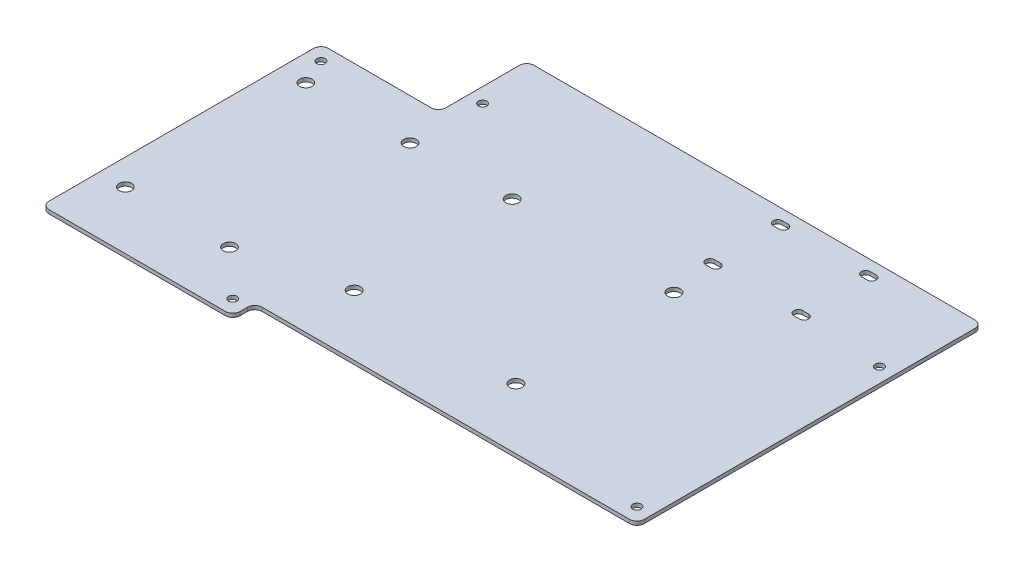
SolidWorks part; units mm, degrees
ref_plane "Front Plane" through (0, 0, 0) normal (0, 0, 1) x (1, 0, 0)
ref_plane "Top Plane" through (0, 0, 0) normal (0, 1, 0) x (1, 0, 0)
ref_plane "Right Plane" through (0, 0, 0) normal (1, 0, 0) x (0, 0, -1)
sketch "Sketch1" plane through (0, 0, 0) normal (0, 1, 0) x (1, 0, 0)
  line L1 (0, 0) -> (247.65, 0)
  line L2 (0, 0) -> (0, 120.65)
  line L3 (50.8, 158.75) -> (247.65, 158.75)
  line L4 (247.65, 0) -> (247.65, 158.75)
  line L15 (0, 120.65) -> (50.8, 120.65)
  line L16 (50.8, 158.75) -> (50.8, 120.65)
  line L21 (351.9786, 184.7613) -> (351.9786, -3.4747) construction
  dimension "D1" = 158.75
  dimension "D2" = 351.9786
  dimension "D4" = 247.65
  dimension "D6" = 38.1
  dimension "D7" = 50.8
extrude "Boss-Extrude1" add sketch "Sketch1" along normal blind 1.6002 contours L1 L4 L3 L2 L15 L16 region at (128.9214, 0, -76.2514)
sketch "Sketch3" plane through (0, 1.6002, 0) normal (0, 1, 0) x (1, 0, 0)
  line L0 (82.55, 0) -> (82.55, 9.525)
  line L1 (0, 0) -> (247.65, 0) construction
  line L2 (82.55, 9.525) -> (247.65, 9.525)
  line L8 (247.65, 0) -> (247.65, 158.75) construction
  line L10 (247.65, 0) -> (82.55, 0)
  line L11 (0, 0) -> (0, 120.65) construction
  line L12 (247.65, 9.525) -> (247.65, 0)
  dimension "D1" = 82.55
  dimension "D2" = 9.525
extrude "Cut-Extrude1" cut sketch "Sketch3" against normal through all
fillet "Fillet1" radius 3.175 8 edges at (82.55, 0.8001, 0) (0, 0.8001, -120.65) (50.8, 0.8001, -120.65) (50.8, 0.8001, -158.75) (247.65, 0.8001, -158.75) (247.65, 0.8001, -9.525) (82.55, 0.8001, -9.525) (0, 0.8001, 0)
sketch "Sketch4" plane through (0, 1.6002, 0) normal (0, 1, 0) x (1, 0, 0)
  line L0 (165.653, 152.32) -> (168.193, 152.32) construction
  line L1 (165.653, 154.225) -> (168.193, 154.225)
  line L2 (165.653, 150.415) -> (168.193, 150.415)
  line L5 (203.753, 152.32) -> (206.293, 152.32) construction
  line L6 (203.753, 154.225) -> (206.293, 154.225)
  line L7 (203.753, 150.415) -> (206.293, 150.415)
  line L8 (203.753, 123.11) -> (206.293, 123.11) construction
  line L9 (203.753, 125.015) -> (206.293, 125.015)
  line L10 (203.753, 121.205) -> (206.293, 121.205)
  line L11 (165.653, 123.11) -> (168.193, 123.11) construction
  line L12 (165.653, 125.015) -> (168.193, 125.015)
  line L13 (165.653, 121.205) -> (168.193, 121.205)
  line L15 (205.023, 123.11) -> (166.923, 123.11) construction
  line L16 (205.023, 123.11) -> (205.023, 152.32) construction
  line L17 (205.023, 152.32) -> (166.923, 152.32) construction
  line L18 (166.923, 123.11) -> (166.923, 152.32) construction
  line L19 (205.023, 123.11) -> (166.923, 152.32) construction
  line L20 (205.023, 152.32) -> (166.923, 123.11) construction
  line L21 (222.488, 125.015) -> (149.458, 125.015) construction
  line L22 (222.488, 125.015) -> (222.488, 150.415) construction
  line L23 (222.488, 150.415) -> (149.458, 150.415) construction
  line L24 (149.458, 125.015) -> (149.458, 150.415) construction
  line L25 (222.488, 125.015) -> (149.458, 150.415) construction
  line L26 (222.488, 150.415) -> (149.458, 125.015) construction
  arc A0 (165.653, 154.225) -> (165.653, 150.415) centre (165.653, 152.32) ccw
  arc A1 (168.193, 150.415) -> (168.193, 154.225) centre (168.193, 152.32) ccw
  arc A2 (203.753, 154.225) -> (203.753, 150.415) centre (203.753, 152.32) ccw
  arc A3 (206.293, 150.415) -> (206.293, 154.225) centre (206.293, 152.32) ccw
  arc A4 (203.753, 125.015) -> (203.753, 121.205) centre (203.753, 123.11) ccw
  arc A5 (206.293, 121.205) -> (206.293, 125.015) centre (206.293, 123.11) ccw
  arc A6 (165.653, 125.015) -> (165.653, 121.205) centre (165.653, 123.11) ccw
  arc A7 (168.193, 121.205) -> (168.193, 125.015) centre (168.193, 123.11) ccw
  point P2 (166.923, 152.32)
  point P12 (185.973, 137.715)
  point P13 (205.023, 152.32)
  point P20 (205.023, 123.11)
  point P27 (166.923, 123.11)
  point P36 (185.973, 137.715)
  dimension "D2" = 6.35
  dimension "D1" = 3.81
  dimension "D5" = 38.1
  dimension "D3" = 2
  dimension "D4" = 2
extrude "Fuse Ziptie Mounts" cut sketch "Sketch4" against normal through all
sketch "Sketch5" plane through (0, 1.6002, 0) normal (0, 1, 0) x (1, 0, 0)
  circle A0 centre (99.298, 103.9876) radius 2.75
  circle A1 centre (99.298, 35.7124) radius 2.75
  circle A2 centre (169.148, 103.9876) radius 2.75
  circle A3 centre (169.148, 35.7124) radius 2.75
  dimension "D1" = 5.5
extrude "Contactor Mounting Holes" cut sketch "Sketch5" against normal through all
sketch "Sketch6" plane through (0, 1.6002, 0) normal (0, 1, 0) x (1, 0, 0)
  line L0 (0, 3.175) -> (0, 117.475) construction
  line L1 (3.175, 120.65) -> (47.625, 120.65) construction
  line L2 (82.55, 6.35) -> (82.55, 3.175) construction
  line L3 (3.175, 0) -> (79.375, 0) construction
  line L4 (244.475, 9.525) -> (85.725, 9.525) construction
  line L5 (247.65, 12.7) -> (247.65, 155.575) construction
  line L6 (53.975, 158.75) -> (244.475, 158.75) construction
  line L7 (50.8, 155.575) -> (50.8, 123.825) construction
  circle A0 centre (6.35, 114.3) radius 1.8288
  circle A1 centre (76.2, 6.35) radius 1.8288
  circle A2 centre (241.3, 15.875) radius 1.8288
  circle A3 centre (241.3, 120.65) radius 1.8288
  circle A4 centre (57.15, 133.35) radius 1.8288
  dimension "D1" = 3.6576
  dimension "D2" = 6.35
  dimension "D3" = 6.35
  dimension "D4" = 6.35
  dimension "D5" = 6.35
  dimension "D6" = 6.35
  dimension "D7" = 6.35
  dimension "D8" = 38.1
  dimension "D9" = 6.35
  dimension "D10" = 25.4
extrude "Cut-Extrude2" cut sketch "Sketch6" against normal through all
sketch "Sketch7" plane through (0, 1.6002, 0) normal (0, 1, 0) x (1, 0, 0)
  circle A0 centre (11.198, 102.95) radius 2.7051
  circle A1 centre (56.198, 102.95) radius 2.7051
  circle A2 centre (11.198, 24.95) radius 2.7051
  circle A3 centre (56.198, 24.95) radius 2.7051
  point P12 (53.1792, 102.95)
  point P13 (53.2915, 102.95)
  point P14 (53.2915, 102.95)
  point P15 (8.2915, 102.95)
  point P16 (51.0355, 102.95)
  point P19 (8.2915, 24.95)
  point P21 (53.2915, 24.95)
  dimension "D1" = 5.4102
extrude "Cut-Extrude3" cut sketch "Sketch7" against normal through all
